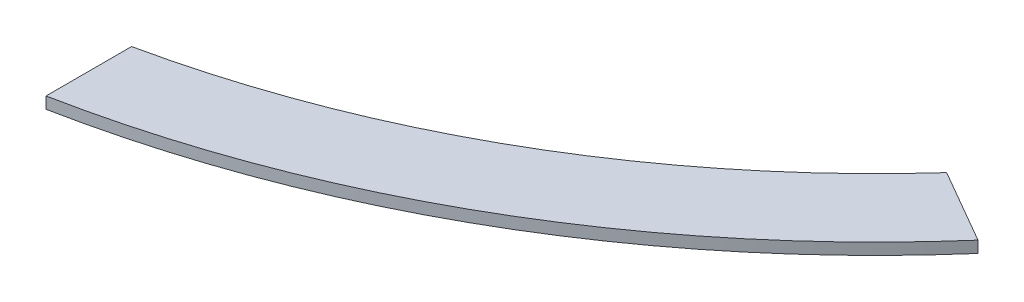
SolidWorks part; units mm, degrees
material "PTFE (general)"
ref_plane "Front Plane" through (0, 0, 0) normal (0, 0, 1) x (1, 0, 0)
ref_plane "Top Plane" through (0, 0, 0) normal (0, 1, 0) x (1, 0, 0)
ref_plane "Right Plane" through (0, 0, 0) normal (1, 0, 0) x (0, 0, -1)
sketch "Sketch1" plane through (0, 0, 0) normal (0, 1, 0) x (1, 0, 0)
  line L0 (-13.335, -62.4087) -> (-13.335, -68.0477)
  line L1 (13.335, -62.4087) -> (13.335, -68.0477)
  line L2 (0, 0) -> (60.0519, -34.671)
  line L3 (47.3801, -42.7528) -> (52.2635, -45.5723)
  line L5 (0, 0) -> (-77.2875, -8.8058) construction
  line L6 (0, 0) -> (0, -23.1086) construction
  circle A0 centre (0, 0) radius 63.8175
  circle A1 centre (0, 0) radius 84.1375
  circle A2 centre (0, 0) radius 67.6275
  circle A5 centre (0, 0) radius 69.342
  point P13 (52.6638, -45.1092)
  dimension "D1" = 127.635
  dimension "D2" = 168.275
  dimension "D4" = 13.335
  dimension "D5" = 13.335
  dimension "D9" = 77.7875
  dimension "D10" = 83.5
  dimension "D7" = 5.5245
  dimension "D6" = 60
  dimension "D8" = 13.335
  dimension "D3" = 3.81
extrude "Boss-Extrude1" add sketch "Sketch1" along normal blind 0.762 contours L1 A2 L3 A0 | L1 A5 L3 A2 region at (32.3203, 0, 55.9804) region at (34.0407, 0, 58.9603)
equation "\"Middle Coupler Inner Daimeter\"= 4.5in"
equation "\"Middle Coupler  Wall Thickness\" = 0.25in"
equation "\"Middle Coupler Bottom Thickness\"= 0.2in"
equation "\"Bearing Rail Offset\"= 0.45in"
equation "\"3-56 UNF Tap\"= 0.089in"
equation "\"3-56 UNF Clearance\"= 0.104in"
equation "\"Ball Bearing Distance\"= 0.03in"
equation "\"D1@Sketch1\"=\"Middle Coupler Inner Daimeter\"+0.5+0.0125*2in"
equation "\"TCA Outer Diameter\" = 6.625in"
equation "\"D2@Sketch1\"=\"TCA Outer Diameter\""
equation "\"D4@Sketch1\"=0.50 + (0.05/2)"
equation "\"D5@Sketch1\"=\"D4@Sketch1\""
equation "\"Interstage Aeroframe Wall Thickness\" = 0.072in"
equation "\"Compression Spring OD\"= 0.42in"
equation "\"10-24 Tap\"= 0.157in"
equation "\"10-24 Clearance\"= 0.196in"
equation "\"D3@Sketch1\"=0.125in+(0.05/2)"
equation "\"Lower Stage Fuselage Wall Thickness\" = 0.25in"
equation "\"6-32 Tap\" = 0.107in"
equation "\"1/4-20 Tap\" = 0.201in"
equation "\"3-48 Tap\"= 0.079in"
equation "\"12-24 Tap\" = 0.177in"
equation "\"3-48 Clearance\" = 0.104in"
equation "\"6-32 Clearance\" = 0.144"
equation "\"D9@Sketch1\"=(\"D2@Sketch1\"-0.5)/2"
equation "\"D1@Boss-Extrude1\"=3/16"
equation "\"D7@Sketch1\"=3/16 + 0.03"
equation "\"D8@Sketch1\"=\"D4@Sketch1\""
